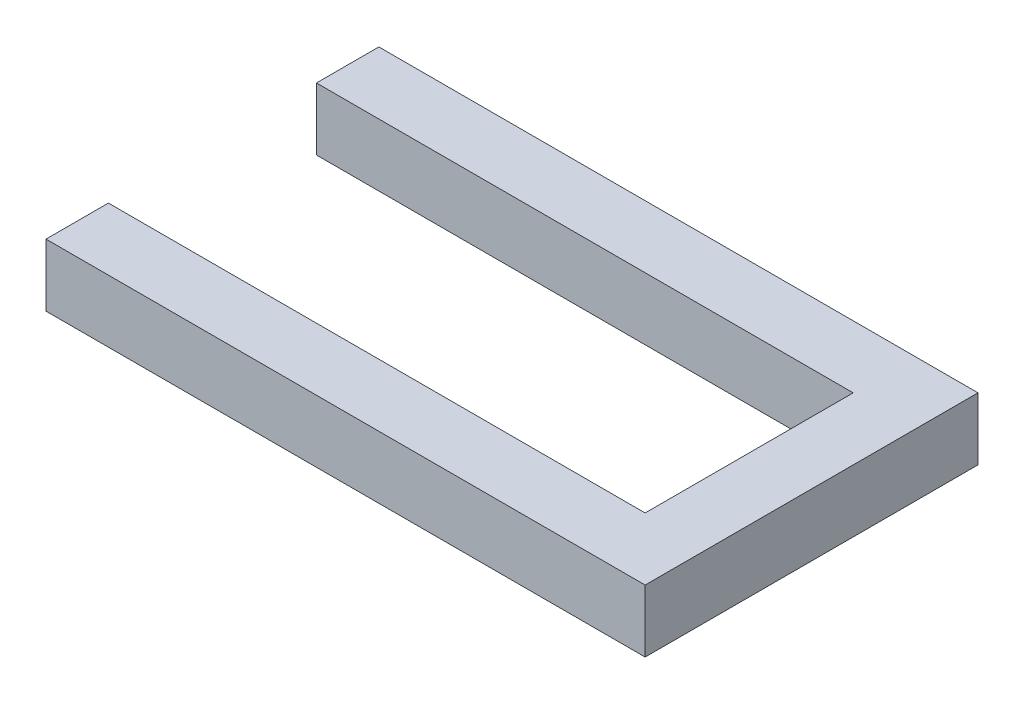
SolidWorks part; units mm, degrees
ref_plane "Front Plane" through (0, 0, 0) normal (0, 0, 1) x (1, 0, 0)
ref_plane "Top Plane" through (0, 0, 0) normal (0, 1, 0) x (1, 0, 0)
ref_plane "Right Plane" through (0, 0, 0) normal (1, 0, 0) x (0, 0, -1)
sketch "Sketch1" plane through (0, 0, 0) normal (0, 0, 1) x (1, 0, 0)
  line L0 (-38.1, 0) -> (38.1, 0) construction
  line L1 (-38.1, 0) -> (0, 0)
  line L2 (-38.1, 0) -> (-38.1, -38.1)
  line L3 (-38.1, -38.1) -> (0, -38.1)
  line L4 (0, 0) -> (0, -38.1)
  line L5 (-38.1, 12.7) -> (-38.1, 0) construction
  dimension "D1" = 38.1
  dimension "D2" = 38.1
extrude "Boss-Extrude1" add sketch "Sketch1" along normal blind 101.6 and the other way blind 101.6
sketch "Sketch2" plane through (-38.1, 0, 0) normal (-1, 0, 0) x (0, 0, 1)
  line L0 (-101.6, 0) -> (101.6, 0) construction
  line L1 (-101.6, -38.1) -> (-63.5, -38.1)
  line L2 (-101.6, -38.1) -> (-101.6, 0)
  line L3 (-101.6, 0) -> (-63.5, 0)
  line L4 (-63.5, -38.1) -> (-63.5, 0)
  line L6 (101.6, -38.1) -> (63.5, -38.1)
  line L7 (101.6, -38.1) -> (101.6, 0)
  line L8 (101.6, 0) -> (63.5, 0)
  line L9 (63.5, -38.1) -> (63.5, 0)
  dimension "D1" = 38.1
  dimension "D2" = 38.1
extrude "Boss-Extrude2" add sketch "Sketch2" along normal up to surface (327.66 mm away)
